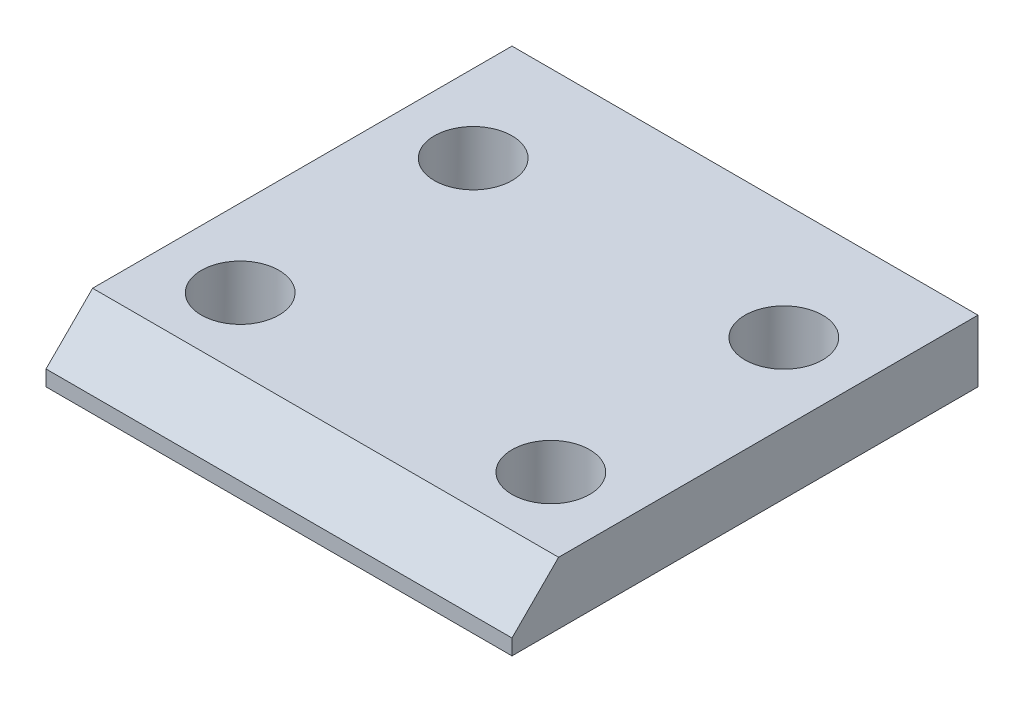
SolidWorks part; units mm, degrees
ref_plane "Front Plane" through (0, 0, 0) normal (0, 0, 1) x (1, 0, 0)
ref_plane "Top Plane" through (0, 0, 0) normal (0, 1, 0) x (1, 0, 0)
ref_plane "Right Plane" through (0, 0, 0) normal (1, 0, 0) x (0, 0, -1)
sketch "Sketch1" plane through (0, 0, 0) normal (0, 1, 0) x (1, 0, 0)
  line L1 (-15, -15) -> (15, -15)
  line L2 (-15, -15) -> (-15, 15)
  line L3 (-15, 15) -> (15, 15)
  line L4 (15, -15) -> (15, 15)
  line L5 (-15, -15) -> (15, 15) construction
  line L6 (-15, 15) -> (15, -15) construction
  point P0 (0, 0)
  dimension "D1" = 30
  dimension "D2" = 30
extrude "Boss-Extrude1" add sketch "Sketch1" along normal blind 3
hole_wizard "Ø1.0mm Dowel Hole1" positions "Sketch3" profile "Sketch4" hole size "Ø1.0" standard "ANSI Metric" end condition through all
sketch "Sketch3" plane through (0, 3, 0) normal (0, 1, 0) x (1, 0, 0)
  line L1 (-10, -7.5) -> (10, -7.5)
  line L2 (-10, -7.5) -> (-10, 7.5)
  line L3 (-10, 7.5) -> (10, 7.5)
  line L4 (10, -7.5) -> (10, 7.5)
  line L5 (-10, -7.5) -> (10, 7.5) construction
  line L6 (-10, 7.5) -> (10, -7.5) construction
  point P57 (0, 0)
  point P60 (-10, 7.5)
  point P63 (10, 7.5)
  point P66 (10, -7.5)
  point P69 (-10, -7.5)
  dimension "D1" = 15
  dimension "D2" = 20
sketch "Sketch4" plane through (-10, 3, 7.5) normal (1, 0, 0) x (0, 0, 1)
  line L0 (0, 0) -> (0, 3)
  line L1 (0, 3) -> (2.5, 3)
  line L2 (2.5, 3) -> (2.5, 0)
  line L5 (2.5, 0) -> (0, 0)
  line L11 (0, -6.35) -> (0, 107.95) construction
  dimension "Thru Hole Dia." = 5
  dimension "Thru Hole Depth" = 3
chamfer "Chamfer2" distance 3 angle 45 1 edges at (0, 3, 15)
sketch "Sketch6" plane through (0, 0, 0) normal (0, -1, 0) x (1, 0, 0)
  line L4 (15, -15) -> (15, 15)
  line L5 (15, 15) -> (-15, 15)
  line L6 (-15, 15) -> (-15, -15)
  line L7 (-15, -15) -> (15, -15)
  line L8 (15, -15) -> (15, 15)
  line L9 (15, 15) -> (-15, 15)
  line L10 (-15, 15) -> (-15, -15)
  line L11 (-15, -15) -> (15, -15)
  circle A0 centre (10, -7.5) radius 2.5 construction
  circle A1 centre (-10, -7.5) radius 2.5 construction
  circle A2 centre (-10, 7.5) radius 2.5 construction
  circle A3 centre (10, 7.5) radius 2.5 construction
  circle A4 centre (10, -7.5) radius 2.5
  circle A5 centre (-10, -7.5) radius 2.5
  circle A6 centre (-10, 7.5) radius 2.5
  circle A7 centre (10, 7.5) radius 2.5
  dimension "D1" = 0
extrude "Boss-Extrude4" add sketch "Sketch6" along normal blind 1
